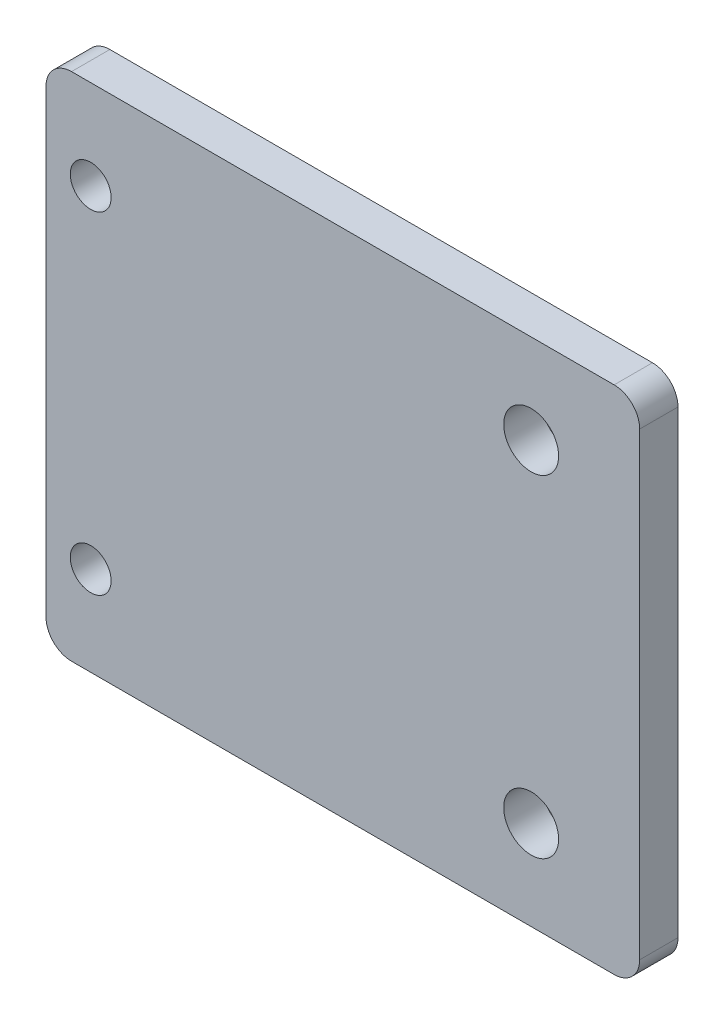
SolidWorks part; units mm, degrees
material "AISI 1045 Steel, cold drawn"
ref_plane "Front Plane" through (0, 0, 0) normal (0, 0, 1) x (1, 0, 0)
ref_plane "Top Plane" through (0, 0, 0) normal (0, 1, 0) x (1, 0, 0)
ref_plane "Right Plane" through (0, 0, 0) normal (1, 0, 0) x (0, 0, -1)
sketch "Sketch1" plane through (0, 0, 0) normal (0, 0, 1) x (1, 0, 0)
  line L1 (23.25, -20) -> (-23.25, -20)
  line L2 (23.25, -20) -> (23.25, 20)
  line L3 (23.25, 20) -> (-23.25, 20)
  line L4 (-23.25, -20) -> (-23.25, 20)
  line L5 (23.25, -20) -> (-23.25, 20) construction
  line L6 (23.25, 20) -> (-23.25, -20) construction
  point P0 (0, 0)
  dimension "D1" = 40
  dimension "D2" = 46.5
extrude "Boss-Extrude1" add sketch "Sketch1" along normal blind 3
sketch "Sketch2" plane through (0, 0, 3) normal (0, 0, 1) x (1, 0, 0)
  line L0 (-23.25, 20) -> (-23.25, -20) construction
  line L1 (14.75, -13) -> (-19.75, -13)
  line L2 (14.75, -13) -> (14.75, 13)
  line L3 (14.75, 13) -> (-19.75, 13)
  line L4 (-19.75, -13) -> (-19.75, 13)
  line L5 (14.75, -13) -> (-19.75, 13) construction
  line L6 (14.75, 13) -> (-19.75, -13) construction
  line L7 (-23.25, 0) -> (-2.5, 0) construction
  point P0 (-2.5, 0)
  dimension "D1" = 34.5
  dimension "D2" = 26
  dimension "D3" = 3.5
hole_wizard "M3 Clearance Hole1" positions "Sketch3" profile "Sketch4" hole size "M3" standard "ANSI Metric"
sketch "Sketch3" plane through (0, 0, 3) normal (0, 0, 1) x (1, 0, 0)
  point P0 (-19.75, 13)
  point P3 (-19.75, -13)
sketch "Sketch4" plane through (-19.75, 13, 3) normal (1, 0, 0) x (0, -1, 0)
  line L0 (0, 0) -> (0, 8.9614)
  line L1 (0, 8.9614) -> (1.6, 8)
  line L2 (1.6, 8) -> (1.6, 0)
  line L5 (1.6, 0) -> (0, 0)
  line L10 (0, 8.9614) -> (-1.6, 8) construction
  line L11 (0, -6.35) -> (0, 107.95) construction
  dimension "Hole Dia." = 3.2
  dimension "Hole Depth" = 8
  dimension "Drill Angle" = 118
hole_wizard "M4 Clearance Hole1" positions "Sketch5" profile "Sketch6" hole size "M4" standard "ANSI Metric"
sketch "Sketch5" plane through (0, 0, 3) normal (0, 0, 1) x (1, 0, 0)
  point P0 (14.75, 13)
  point P3 (14.75, -13)
sketch "Sketch6" plane through (14.75, 13, 3) normal (1, 0, 0) x (0, -1, 0)
  line L0 (0, 0) -> (0, 9.2919)
  line L1 (0, 9.2919) -> (2.15, 8)
  line L2 (2.15, 8) -> (2.15, 0)
  line L5 (2.15, 0) -> (0, 0)
  line L10 (0, 9.2919) -> (-2.15, 8) construction
  line L11 (0, -6.35) -> (0, 107.95) construction
  dimension "Hole Dia." = 4.3
  dimension "Hole Depth" = 8
  dimension "Drill Angle" = 118
fillet "Fillet1" radius 2 4 edges at (23.25, 20, 1.5) (23.25, -20, 1.5) (-23.25, -20, 1.5) (-23.25, 20, 1.5)
